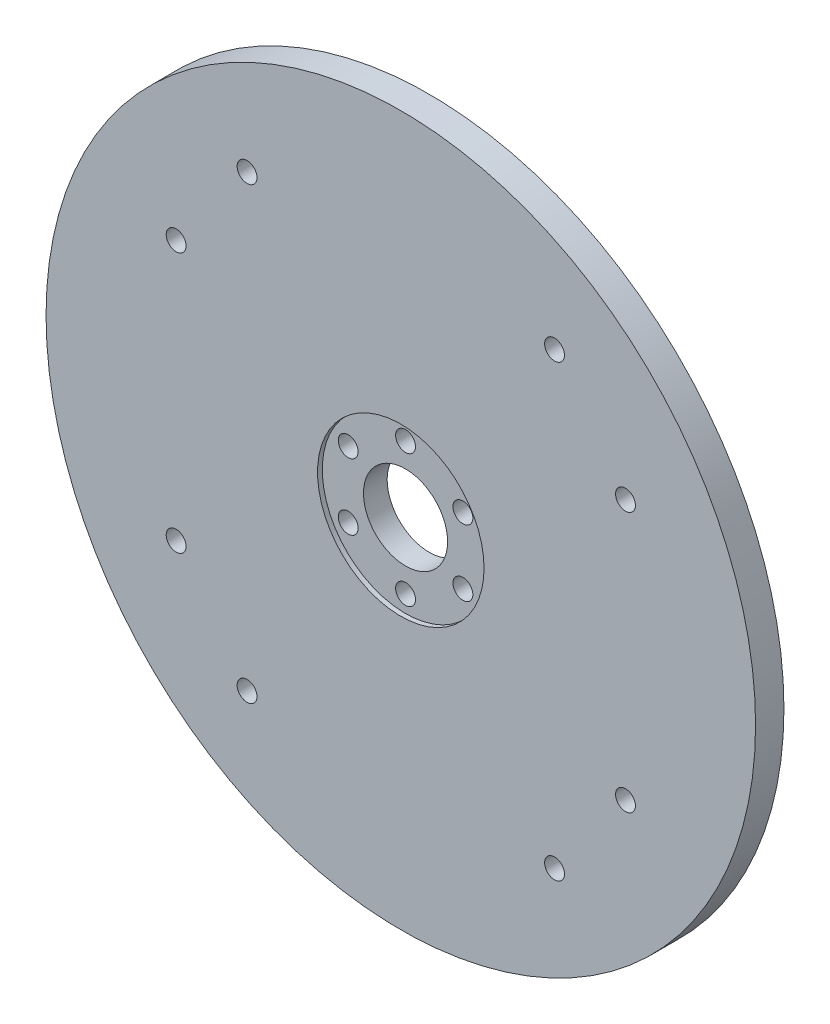
SolidWorks part; units mm, degrees
ref_plane "前视基准面" through (0, 0, 0) normal (0, 0, 1) x (1, 0, 0)
ref_plane "上视基准面" through (0, 0, 0) normal (0, 1, 0) x (1, 0, 0)
ref_plane "右视基准面" through (0, 0, 0) normal (1, 0, 0) x (0, 0, -1)
other "Configuration Table"
sketch "草图1" plane through (0, 0, 0) normal (0, 0, 1) x (1, 0, 0)
  circle A0 centre (0, 0) radius 40
extrude "凸台-拉伸1" add sketch "草图1" along normal blind 2
sketch "草图2" plane through (0, 0, 2) normal (0, 0, 1) x (1, 0, 0)
  circle A0 centre (0, 0) radius 34
  dimension "D1" = 68
extrude "切除-拉伸1" cut sketch "草图2" against normal blind 0.5
sketch "草图3" plane through (0, 0, 1.5) normal (0, 0, 1) x (1, 0, 0)
  circle A0 centre (0, 0) radius 17.5
  dimension "D1" = 35
extrude "切除-拉伸4" cut sketch "草图3" against normal blind 1
sketch "草图5" plane through (0, 0, 0.5) normal (0, 0, 1) x (1, 0, 0)
  circle A0 centre (0, 0) radius 14
  circle A1 centre (0, 14) radius 2
  circle A2 centre (12.1244, 7) radius 2
  circle A3 centre (12.1244, -7) radius 2
  circle A4 centre (0, -14) radius 2
  circle A5 centre (-12.1244, -7) radius 2
  circle A6 centre (-12.1244, 7) radius 2
  point P18 (0, 0)
  dimension "D1" = 6
extrude "切除-拉伸5" cut sketch "草图5" against normal blind 1 contours A1 | A2 | A3 | A4 | A5 | A6
sketch "草图6" plane through (0, 0, 0) normal (0, 0, -1) x (-1, 0, 0)
  circle A0 centre (0, 0) radius 8
extrude "切除-拉伸6" cut sketch "草图6" against normal blind 10
sketch "草图7" plane through (0, 0, 0) normal (0, 0, -1) x (-1, 0, 0)
  circle A0 centre (0, 14) radius 2.1
  circle A1 centre (12.1244, 7) radius 2.1
  circle A2 centre (12.1244, -7) radius 2.1
  circle A3 centre (0, -14) radius 2.1
  circle A4 centre (-12.1244, -7) radius 2.1
  circle A5 centre (-12.1244, 7) radius 2.1
  point P15 (0, 0)
  dimension "D1" = 6
extrude "切除-拉伸7" cut sketch "草图7" against normal blind 10
sketch "草图8" plane through (0, 0, 0) normal (0, 0, -1) x (-1, 0, 0)
  circle A0 centre (0, 0) radius 40
  circle A1 centre (0, 0) radius 70
extrude "凸台-拉伸2" add sketch "草图8" against normal blind 2
sketch "草图9" plane through (0, 0, 0) normal (0, 0, -1) x (-1, 0, 0)
  line L0 (0.8061, -59.9946) -> (-0.8061, 59.9946)
  line L1 (35.2462, 60.479) -> (-36.8583, 59.5102)
  line L2 (60, 0) -> (-60, 0)
  line L3 (-60, 36.0555) -> (-60, -36.0555)
  line L4 (-36.8583, 59.5102) -> (-36.8583, 159.5102)
  line L5 (-36.8583, 159.5102) -> (35.2462, 159.5102)
  line L6 (35.2462, 159.5102) -> (35.2462, 60.479)
  line L7 (60, 36.0555) -> (160, 36.0555)
  line L8 (160, 36.0555) -> (160, -36.0555)
  line L9 (160, -36.0555) -> (60, -36.0555)
  line L10 (-36.8583, -59.5102) -> (-36.8583, -160.479)
  line L11 (-36.8583, -160.479) -> (35.2462, -160.479)
  line L12 (35.2462, -160.479) -> (35.2462, -60.479)
  line L13 (-60, 36.0555) -> (-160, 36.0555)
  line L14 (-160, 36.0555) -> (-160, -36.0555)
  line L15 (-160, -36.0555) -> (-60, -36.0555)
  circle A0 centre (0, 0) radius 70 construction
  circle A1 centre (0, 0) radius 70
  point P5 (0, 0)
  point P10 (-0.8061, 59.9946)
  point P15 (0, 0)
  circle M20 centre (0, 0) radius 70
extrude "凸台-拉伸3" add sketch "草图9" against normal blind 2 contours L6 L5 L4 M20 | L9 L8 L7 M20 | L11 L12 L10 M20 | L14 L15 L13 M20 region at (0.8649, 113.0896, 0) region at (113.3375, 0, 0) region at (-113.3375, 0, 0) region at (0.8643, -113.5744, 0)
sketch "草图11" plane through (0, 0, 0) normal (0, 0, -1) x (-1, 0, 0)
  circle A1 centre (0, 0) radius 75
  circle A2 centre (0, -14) radius 2.1 construction
  circle A3 centre (-12.1244, -7) radius 2.1 construction
  circle A4 centre (-12.1244, 7) radius 2.1 construction
  circle A5 centre (0, 0) radius 8 construction
  circle A6 centre (12.1244, -7) radius 2.1 construction
  circle A7 centre (12.1244, 7) radius 2.1 construction
  circle A8 centre (0, 14) radius 2.1 construction
  circle A9 centre (0, -14) radius 2.1
  circle A10 centre (-12.1244, -7) radius 2.1
  circle A11 centre (-12.1244, 7) radius 2.1
  circle A12 centre (0, 0) radius 8
  circle A13 centre (12.1244, -7) radius 2.1
  circle A14 centre (12.1244, 7) radius 2.1
  circle A15 centre (0, 14) radius 2.1
  point P6 (0, 0)
  dimension "D1" = 150
extrude "凸台-拉伸4" add sketch "草图11" against normal blind 2
sketch "草图13" plane through (0, 0, 0) normal (0, 0, -1) x (-1, 0, 0)
  line L0 (-160, -18) -> (-160, 18)
  line L1 (-160, 36.0555) -> (-160, -36.0555) construction
  line L2 (18, 159.5102) -> (-18, 159.5102)
  line L3 (-36.8583, 159.5102) -> (35.2462, 159.5102) construction
  line L4 (160, -18) -> (160, 18)
  line L5 (160, 36.0555) -> (160, -36.0555) construction
  line L6 (18, -160.479) -> (-18, -160.479)
  line L7 (-36.8583, -160.479) -> (35.2462, -160.479) construction
  line L8 (-18, -160.479) -> (-18, -64.2372)
  line L9 (-18, -64.2372) -> (18, -64.2372)
  line L10 (18, -64.2372) -> (18, -160.479)
  line L11 (160, -18) -> (52.464, -18)
  line L12 (52.464, -18) -> (52.464, 18)
  line L13 (52.464, 18) -> (157.6491, 18)
  line L14 (157.6491, 18) -> (160, 18)
  line L15 (-18, 159.5102) -> (-18, 59.373)
  line L16 (-18, 59.373) -> (18, 59.373)
  line L17 (18, 59.373) -> (18, 159.5102)
  line L18 (-160, 18) -> (-64.3037, 18)
  line L19 (-64.3037, 18) -> (-64.3037, -18)
  line L20 (-64.3037, -18) -> (-160, -18)
  point P5 (-160, 0)
  point P11 (0, 159.5102)
  point P16 (160, 0)
  point P21 (0, -160.479)
extrude "切除-拉伸10" cut sketch "草图13" against normal blind 198
extrude "凸台-拉伸5" add sketch "草图11<3>" against normal blind 2
sketch "草图11<3>" plane through (0, 0, 0) normal (0, 0, -1) x (-1, 0, 0) same geometry as "草图11"
sketch "草图17" plane through (0, 0, 0) normal (0, 0, -1) x (-1, 0, 0)
  line L0 (-160, 27.0278) -> (-157.6, 27.0278)
  line L1 (-160, 36.0555) -> (-160, 18) construction
  line L2 (-157.6, 27.0278) -> (-132.6, 27.0278)
  circle A0 centre (-157.6, 27.0278) radius 1.65
  circle A1 centre (-132.6, 27.0278) radius 1.65
  circle A2 centre (-157.6, -27.0278) radius 1.65
  circle A3 centre (-132.6, -27.0278) radius 1.65
  circle A4 centre (27.0278, 157.6) radius 1.65
  circle A5 centre (27.0278, 132.6) radius 1.65
  circle A6 centre (-27.0278, 157.6) radius 1.65
  circle A7 centre (-27.0278, 132.6) radius 1.65
  circle A8 centre (157.6, -27.0278) radius 1.65
  circle A9 centre (132.6, -27.0278) radius 1.65
  circle A10 centre (157.6, 27.0278) radius 1.65
  circle A11 centre (132.6, 27.0278) radius 1.65
  circle A12 centre (-27.0278, -157.6) radius 1.65
  circle A13 centre (-27.0278, -132.6) radius 1.65
  circle A14 centre (27.0278, -157.6) radius 1.65
  circle A15 centre (27.0278, -132.6) radius 1.65
  point P38 (0, 0)
  dimension "D1" = 3.3
  dimension "D2" = 3.3
  dimension "D3" = 3.3
  dimension "D4" = 3.3
  dimension "D5" = 4
extrude "切除-拉伸12" cut sketch "草图17" against normal blind 280 contours A6 | A7 | A5 | A11 | A12 | A0 | A1 | A2 | A3 | A4 | A10 | A13 | A15 | A14 region at (-27.0278, 132.6, 0) region at (27.0278, 157.6, 0) region at (27.0278, 132.6, 0) region at (-132.6, 27.0278, 0) region at (27.0278, -157.6, 0)
sketch "草图18" plane through (0, 0, 0) normal (0, 0, -1) x (-1, 0, 0)
  line L0 (160, 36.0555) -> (160, 18)
  line L1 (72.7684, 18.1594) -> (72.808, -18)
  line L2 (132.6, 27.0278) -> (157.6, 27.0278)
  line L3 (157.6, 27.0278) -> (160, 27.0278)
  circle A0 centre (0, 0) radius 75
  circle A1 centre (157.6, 27.0278) radius 1.65
  circle A2 centre (0, 0) radius 234.865
  dimension "D1" = 3.3
extrude "切除-拉伸13" cut sketch "草图18" against normal blind 222 contours A2 A0 A1 region at (228.222, 0, 0)
sketch "草图20" plane through (0, 0, 0) normal (0, 0, -1) x (-1, 0, 0)
  circle A0 centre (0, 0) radius 8.8884
extrude "切除-拉伸15" cut sketch "草图20" against normal blind 17
sketch "草图28" plane through (0, 0, 2) normal (0, 0, 1) x (1, 0, 0)
  circle A0 centre (0, 0) radius 17.5
  dimension "D1" = 35
extrude "切除-拉伸16" cut sketch "草图28" against normal blind 1
sketch "草图30" plane through (0, 0, 0) normal (0, 0, -1) x (-1, 0, 0)
  line L0 (0, -47.5) -> (0, 47.5)
  line L1 (32.5, -47.5) -> (-32.5, -47.5)
  circle A0 centre (-32.5, -47.5) radius 2.1
  circle A1 centre (32.5, -47.5) radius 2.1
  circle A8 centre (-32.5, 47.5) radius 2.1
  circle A9 centre (32.5, 47.5) radius 2.1
  point P5 (0, 0)
  point P9 (0, -47.5)
  dimension "D1" = 4.2
  dimension "D2" = 4.2
  dimension "D3" = 4.2
  dimension "D4" = 4.2
  dimension "D5" = 4.2
sketch "草图33" plane through (0, 0, 0) normal (0, 0, -1) x (-1, 0, 0)
  line L0 (47.5, 0) -> (-47.5, 0)
  line L1 (-47.5, -27.5) -> (-47.5, 27.5)
  circle A0 centre (-47.5, 27.5) radius 2.1
  circle A1 centre (-47.5, -27.5) radius 2.1
  circle A4 centre (47.5, 27.5) radius 2.1
  circle A5 centre (47.5, -27.5) radius 2.1
  point P5 (0, 0)
  point P9 (-47.5, 0)
  dimension "D1" = 4.2
  dimension "D2" = 4.2
  dimension "D3" = 4.2
  dimension "D4" = 4.2
sketch "草图34" plane through (0, 0, 2) normal (0, 0, 1) x (1, 0, 0)
  circle A0 centre (0, 0) radius 17.6
  dimension "D1" = 35.2
extrude "切除-拉伸22" cut sketch "草图34" against normal blind 1
extrude "切除-拉伸27" cut sketch "草图30" against normal blind 10 contours A8 | A9 | A1 | A0
extrude "切除-拉伸28" cut sketch "草图33" against normal blind 10 contours A0 | A4 | A5 | A1
sketch "草图40" plane through (0, 0, 0) normal (0, 0, -1) x (-1, 0, 0)
  circle A0 centre (0, 0) radius 75
  circle A1 centre (0, 0) radius 8.8884
  circle A2 centre (-12.1244, 7) radius 2.1 construction
  circle A3 centre (-12.1244, -7) radius 2.1 construction
  circle A4 centre (0, -14) radius 2.1 construction
  circle A5 centre (12.1244, -7) radius 2.1 construction
  circle A6 centre (12.1244, 7) radius 2.1 construction
  circle A7 centre (0, 14) radius 2.1 construction
  circle A8 centre (32.5, 47.5) radius 2.1 construction
  circle A9 centre (47.5, 27.5) radius 2.1 construction
  circle A10 centre (47.5, -27.5) radius 2.1 construction
  circle A11 centre (32.5, -47.5) radius 2.1 construction
  circle A12 centre (-32.5, -47.5) radius 2.1 construction
  circle A13 centre (-47.5, -27.5) radius 2.1 construction
  circle A14 centre (-47.5, 27.5) radius 2.1 construction
  circle A15 centre (-32.5, 47.5) radius 2.1 construction
  circle A16 centre (-12.1244, 7) radius 2.1
  circle A17 centre (-12.1244, -7) radius 2.1
  circle A18 centre (0, -14) radius 2.1
  circle A19 centre (12.1244, -7) radius 2.1
  circle A20 centre (12.1244, 7) radius 2.1
  circle A21 centre (0, 14) radius 2.1
  circle A22 centre (32.5, 47.5) radius 2.1
  circle A23 centre (47.5, 27.5) radius 2.1
  circle A24 centre (47.5, -27.5) radius 2.1
  circle A25 centre (32.5, -47.5) radius 2.1
  circle A26 centre (-32.5, -47.5) radius 2.1
  circle A27 centre (-47.5, -27.5) radius 2.1
  circle A28 centre (-47.5, 27.5) radius 2.1
  circle A29 centre (-32.5, 47.5) radius 2.1
extrude "凸台-拉伸6" add sketch "草图40" along normal blind 4
